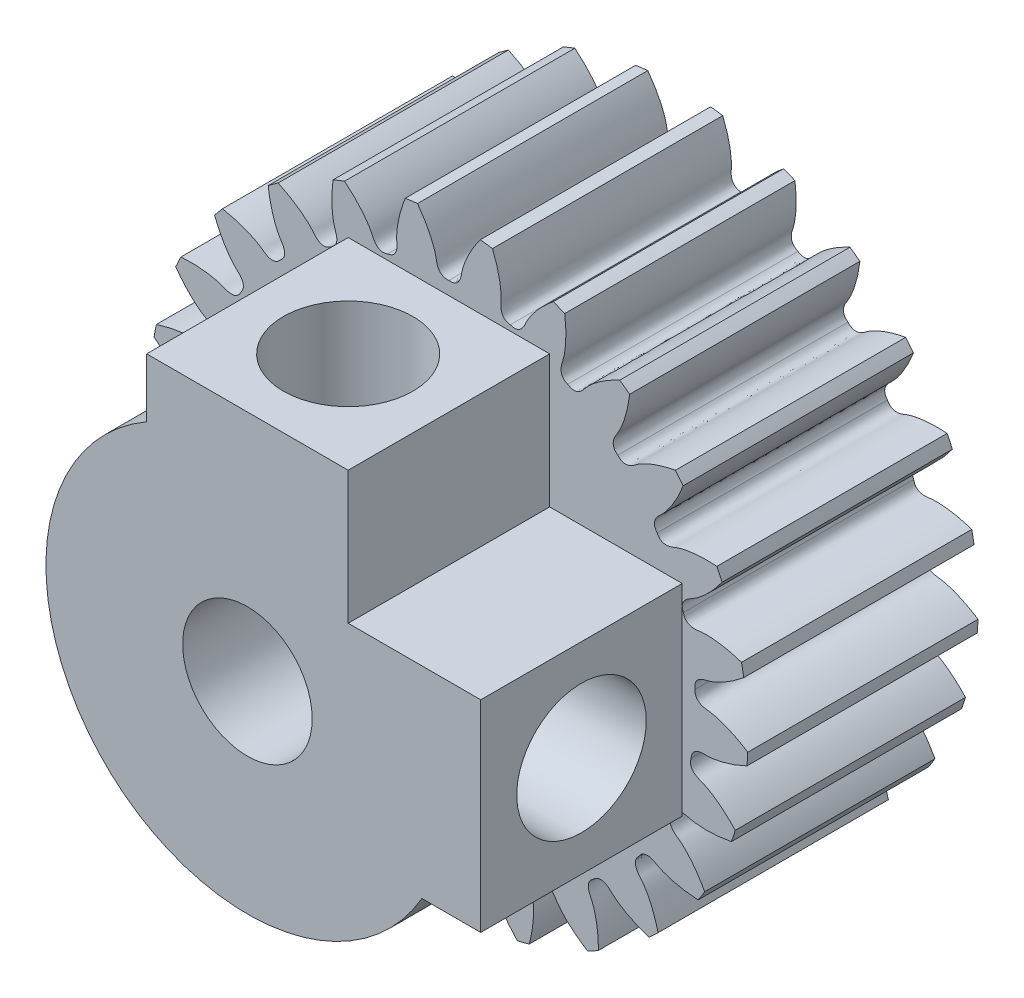
SolidWorks part; units mm, degrees
material "PLA Black"
ref_plane "Front" through (0, 0, 0) normal (0, 0, 1) x (1, 0, 0)
ref_plane "Top" through (0, 0, 0) normal (0, 1, 0) x (1, 0, 0)
ref_plane "Right" through (0, 0, 0) normal (1, 0, 0) x (0, 0, -1)
ref_axis "Axis1" through (0, 0, -15.6032) along (0, 0, 1)
sketch "Gear-BaseSketch" plane through (0, 0, 0) normal (0, 0, 1) x (1, 0, 0)
  circle A0 centre (0, 0) radius 10.3909
  dimension "D1" = 20.7818
extrude "33.0 Diametral Pitch, 20.78mm P.D." add sketch "Gear-BaseSketch" along normal mid plane 8
sketch "Tooth-Sketch; Backlash: 0.0000mm" plane through (0, 0, 0) normal (0, 0, 1) x (1, 0, 0)
  line L0 (0, 0) -> (0, 10.3909) construction
  arc A0 (-1.0905, 10.334) -> (1.0905, 10.334) centre (0, -0.094) cw
  circle A1 centre (0, 0) radius 10.3909 construction
  spline S0 degree 3 poles (-1.0905, 10.334) (-1.0138, 10.2299) (-0.9082, 10.0753) (-0.7851, 9.8689) (-0.7088, 9.729) (-0.6442, 9.5985) (-0.5903, 9.4783) (-0.5464, 9.369) (-0.5115, 9.2711) (-0.4845, 9.1851) (-0.4645, 9.1115) (-0.4506, 9.0507) (-0.4416, 9.0039) (-0.4365, 8.9698) (-0.432, 8.9444) (-0.4246, 8.9083) (-0.4122, 8.8596) (-0.3912, 8.7995) (-0.3638, 8.742) (-0.3272, 8.686) (-0.2761, 8.6321) (-0.1724, 8.5642) (-0.0681, 8.5594) (0, 8.5647) knots 0 0 0 0 0.176711 0.2556 0.328177 0.394444 0.454399 0.508044 0.555377 0.596399 0.63111 0.65951 0.681599 0.696189 0.706616 0.716848 0.746535 0.775185 0.80367 0.83335 0.866218 0.904587 1 1 1 1
  spline S1 degree 3 poles (1.0905, 10.334) (1.0138, 10.2299) (0.9082, 10.0753) (0.7851, 9.8689) (0.7088, 9.729) (0.6442, 9.5985) (0.5903, 9.4783) (0.5464, 9.369) (0.5115, 9.2711) (0.4845, 9.1851) (0.4645, 9.1115) (0.4506, 9.0507) (0.4416, 9.0039) (0.4365, 8.9698) (0.432, 8.9444) (0.4246, 8.9083) (0.4122, 8.8596) (0.3912, 8.7995) (0.3638, 8.742) (0.3272, 8.686) (0.2761, 8.6321) (0.1724, 8.5642) (0.0681, 8.5594) (0, 8.5647) knots 0 0 0 0 0.176711 0.2556 0.328177 0.394444 0.454399 0.508044 0.555377 0.596399 0.63111 0.65951 0.681599 0.696189 0.706616 0.716848 0.746535 0.775185 0.80367 0.83335 0.866218 0.904587 1 1 1 1
extrude "Tooth-Cut, Fine Pitch Involute 20 deg" cut sketch "Tooth-Sketch; Backlash: 0.0000mm" against normal through all and the other way through all
pattern_circular "Tooth Pattern, 25 / 25" count 25 over 360 about axis through (0, 0, -15.6032) along (0, 0, 1) of "Tooth-Cut, Fine Pitch Involute 20 deg"
sketch "Sketch4" plane through (0, 0, 4) normal (0, 0, 1) x (1, 0, 0)
  circle A0 centre (0, 0) radius 2.25
  dimension "D1" = 4.5
extrude "Cut-Extrude2" cut sketch "Sketch4" against normal through all contours A0
sketch "Sketch6" plane through (0, 0, 4) normal (0, 0, 1) x (1, 0, 0)
  line L0 (8.1057, 3.5) -> (8.1057, -3.5)
  line L1 (8.1057, -3.5) -> (6.0622, -3.5)
  line L2 (8.1057, 3.5) -> (3.5, 3.5)
  line L3 (3.5, 3.5) -> (3.5, 8.1057)
  line L4 (3.5, 8.1057) -> (-3.5, 8.1057)
  line L5 (-3.5, 8.1057) -> (-3.5, 6.0622)
  line L6 (0, 0) -> (16.4498, 0) construction
  line L7 (0, 0) -> (0, 8.1057) construction
  circle A1 centre (0, 0) radius 2.25
  circle A2 centre (0, 0) radius 2.25 construction
  arc A3 (6.0622, -3.5) -> (-3.5, 6.0622) centre (0, 0) cw
  spline S0 degree 3 poles (9.4909, 4.2301) (9.4157, 4.1251) (9.3014, 3.977) (9.1433, 3.7963) (9.0338, 3.6805) (8.9297, 3.5787) (8.832, 3.4904) (8.7416, 3.4149) (8.6593, 3.3514) (8.5858, 3.2992) (8.522, 3.2574) (8.4685, 3.2253) (8.4268, 3.2024) (8.3959, 3.187) (8.3732, 3.1748) (8.3411, 3.1567) (8.2986, 3.1298) (8.248, 3.0912) (8.2017, 3.0475) (8.1598, 2.9953) (8.1243, 2.93) (8.0917, 2.8105) (8.1194, 2.7097) (8.1455, 2.6466) knots 0.000271 0.000271 0.000271 0.000271 0.176711 0.2556 0.328177 0.394444 0.454399 0.508044 0.555377 0.596399 0.63111 0.65951 0.681599 0.696189 0.706616 0.716848 0.746535 0.775185 0.80367 0.83335 0.866218 0.904587 1 1 1 1 construction
  dimension "D1" = 7
  dimension "D2" = 7
extrude "Boss-Extrude2" add sketch "Sketch6" along normal blind 7
sketch "Sketch10" plane through (0, 8.1057, 0) normal (0, 1, 0) x (1, 0, 0)
  line L0 (-3.5, -7.5) -> (3.5, -7.5) construction
  line L3 (0, -4) -> (0, -11) construction
  line L5 (-3.5, -11) -> (-3.5, -4) construction
  line L6 (3.5, -11) -> (3.5, -4) construction
  line L7 (3.5, -11) -> (-3.5, -11) construction
  circle A0 centre (0, -7.5) radius 2.25
  dimension "D1" = 4.5
extrude "Cut-Extrude3" cut sketch "Sketch10" against normal blind 8
sketch "Sketch11" plane through (8.1057, 0, 0) normal (1, 0, 0) x (0, 0, -1)
  line L0 (-7.5, 3.5) -> (-7.5, -3.5) construction
  line L5 (-11, 3.5) -> (-4, 3.5) construction
  line L6 (-11, -3.5) -> (-4, -3.5) construction
  circle A0 centre (-7.5, 0) radius 2.25
  dimension "D1" = 4.5
extrude "Cut-Extrude4" cut sketch "Sketch11" against normal blind 8 contours A0
